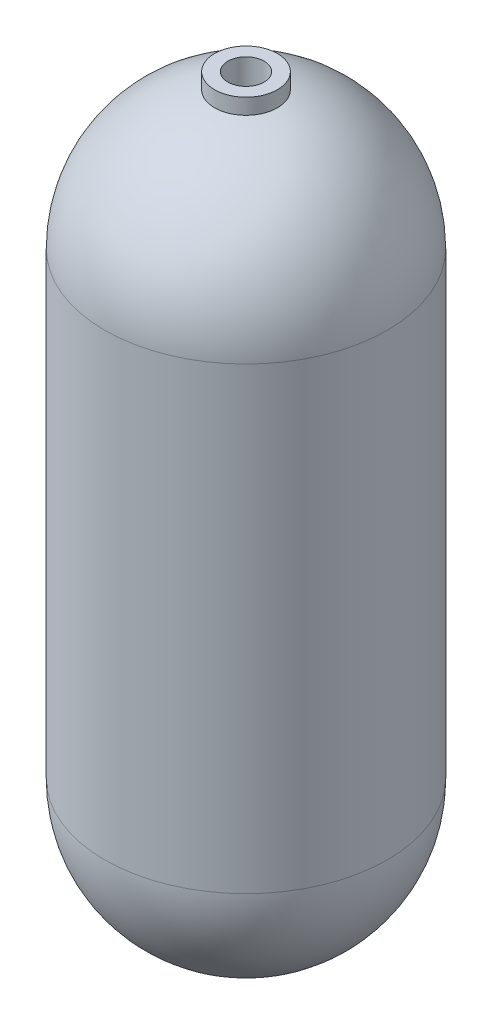
SolidWorks part; units mm, degrees
ref_plane "Front Plane" through (0, 0, 0) normal (0, 0, 1) x (1, 0, 0)
ref_plane "Top Plane" through (0, 0, 0) normal (0, 1, 0) x (1, 0, 0)
ref_plane "Right Plane" through (0, 0, 0) normal (1, 0, 0) x (0, 0, -1)
sketch "Sketch4" plane through (0, 0, 0) normal (0, 0, 1) x (1, 0, 0)
  line L0 (0, 80.4479) -> (0, -242.729) construction
  line L1 (12.7, 62.071) -> (12.7, 55.721)
  line L3 (57.15, 0) -> (57.15, -185.579)
  line L4 (50.8, 0) -> (50.8, -185.579)
  line L5 (0, -236.379) -> (0, -242.729)
  line L6 (6.35, 62.071) -> (12.7, 62.071)
  line L7 (6.35, 62.071) -> (2.54, 62.071)
  line L8 (2.54, 62.071) -> (2.54, 50.7365)
  line L9 (6.35, 62.071) -> (6.35, 50.4016) construction
  arc A0 (57.15, -185.579) -> (0, -242.729) centre (0, -185.579) cw
  arc A1 (57.15, 0) -> (12.7, 55.721) centre (0, 0) ccw
  arc A2 (50.8, 0) -> (6.35, 50.4016) centre (0, 0) ccw
  arc A3 (50.8, -185.579) -> (0, -236.379) centre (0, -185.579) cw
  arc A4 (6.35, 50.4016) -> (2.54, 50.7365) centre (0, 0) ccw
  dimension "D3" = 304.8
  dimension "D1" = 12.7
  dimension "D2" = 57.15
  dimension "D4" = 6.35
  dimension "D6" = 10.16
  dimension "D5" = 6.35
revolve "Revolve1" add sketch "Sketch4" angle 360 about L0
hole_wizard "5/8-18 Tapped Hole2" positions "Sketch8" profile "Sketch7" tap size "5/8-18" standard "ANSI Inch"
sketch "Sketch8" plane through (0, 62.071, 0) normal (0, 1, 0) x (1, 0, 0)
  point P0 (0, 0)
sketch "Sketch7" plane through (0, 62.071, 0) normal (1, 0, 0) x (0, 0, 1)
  line L0 (0, 0) -> (0, 43.2734)
  line L1 (0, 43.2734) -> (7.3419, 38.862)
  line L2 (7.3419, 38.862) -> (7.3419, 0)
  line L5 (7.3419, 0) -> (0, 0)
  line L10 (0, 43.2734) -> (-7.3419, 38.862) construction
  line L11 (0, -6.35) -> (0, 107.95) construction
  dimension "Tap Drill Dia." = 14.6837
  dimension "Tap Drill Depth" = 38.862
  dimension "Drill Angle" = 118
cosmetic thread "Hole Thread1" parameters "D1"=11.6974, "D2"=15.875
